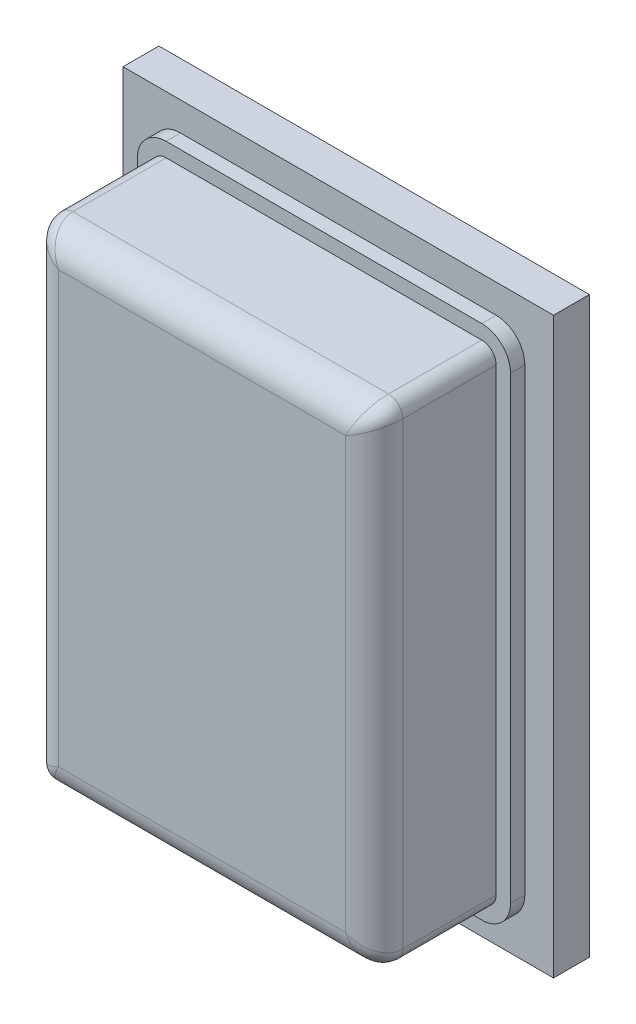
SolidWorks part; units mm, degrees
ref_plane "Спереди" through (0, 0, 0) normal (0, 0, 1) x (1, 0, 0)
ref_plane "Сверху" through (0, 0, 0) normal (0, 1, 0) x (1, 0, 0)
ref_plane "Справа" through (0, 0, 0) normal (1, 0, 0) x (0, 0, -1)
sketch "Sketch1" plane through (0, 0, 0) normal (0, 0, 1) x (1, 0, 0)
  line L1 (-1.5, -2) -> (1.5, -2)
  line L2 (-1.5, -2) -> (-1.5, 2)
  line L3 (-1.5, 2) -> (1.5, 2)
  line L4 (1.5, -2) -> (1.5, 2)
  line L5 (-1.5, -2) -> (1.5, 2) construction
  line L6 (-1.5, 2) -> (1.5, -2) construction
  point P0 (0, 0)
  dimension "D1" = 3
  dimension "D2" = 4
extrude "Boss-Extrude1" add sketch "Sketch1" along normal blind 0.25
sketch "Sketch2" plane through (0, 0, 0.25) normal (0, 0, 1) x (1, 0, 0)
  line L12 (1.3, -1.8) -> (1.3, 1.8)
  line L13 (1.3, 1.8) -> (-1.3, 1.8)
  line L14 (-1.3, 1.8) -> (-1.3, -1.8)
  line L15 (-1.3, -1.8) -> (1.3, -1.8)
  line L16 (1.3, -1.6) -> (1.3, 1.6)
  line L17 (1.1, 1.8) -> (-1.1, 1.8)
  line L18 (-1.3, 1.6) -> (-1.3, -1.6)
  line L19 (-1.1, -1.8) -> (1.1, -1.8)
  arc A0 (1.3, 1.6) -> (1.1, 1.8) centre (1.1, 1.6) ccw
  arc A1 (1.1, -1.8) -> (1.3, -1.6) centre (1.1, -1.6) ccw
  arc A2 (-1.3, -1.6) -> (-1.1, -1.8) centre (-1.1, -1.6) ccw
  arc A3 (-1.3, 1.6) -> (-1.1, 1.8) centre (-1.1, 1.6) cw
  dimension "D2" = 0.2
  dimension "D1" = 0.2
extrude "Boss-Extrude2" add sketch "Sketch2" along normal blind 0.1
sketch "Sketch3" plane through (0, 0, 0.35) normal (0, 0, 1) x (1, 0, 0)
  line L8 (1.1, 1.7) -> (-1.1, 1.7)
  line L9 (-1.2, 1.6) -> (-1.2, -1.6)
  line L10 (-1.1, -1.7) -> (1.1, -1.7)
  line L11 (1.2, -1.6) -> (1.2, 1.6)
  line L12 (1.1, 1.7) -> (-1.1, 1.7)
  line L13 (-1.2, 1.6) -> (-1.2, -1.6)
  line L14 (-1.1, -1.7) -> (1.1, -1.7)
  line L15 (1.2, -1.6) -> (1.2, 1.6)
  arc A8 (1.2, 1.6) -> (1.1, 1.7) centre (1.1, 1.6) ccw
  arc A9 (-1.1, 1.7) -> (-1.2, 1.6) centre (-1.1, 1.6) ccw
  arc A10 (-1.2, -1.6) -> (-1.1, -1.7) centre (-1.1, -1.6) ccw
  arc A11 (1.1, -1.7) -> (1.2, -1.6) centre (1.1, -1.6) ccw
  arc A12 (1.2, 1.6) -> (1.1, 1.7) centre (1.1, 1.6) ccw
  arc A13 (-1.1, 1.7) -> (-1.2, 1.6) centre (-1.1, 1.6) ccw
  arc A14 (-1.2, -1.6) -> (-1.1, -1.7) centre (-1.1, -1.6) ccw
  arc A15 (1.1, -1.7) -> (1.2, -1.6) centre (1.1, -1.6) ccw
  dimension "D1" = 0.1
extrude "Boss-Extrude3" add sketch "Sketch3" along normal blind 0.85
fillet "Fillet1" radius 0.2 8 edges at (1.1707, 1.6707, 1.2) (1.2, 0, 1.2) (1.1707, -1.6707, 1.2) (0, -1.7, 1.2) (-1.1707, -1.6707, 1.2) (-1.2, 0, 1.2) (-1.1707, 1.6707, 1.2) (0, 1.7, 1.2)
